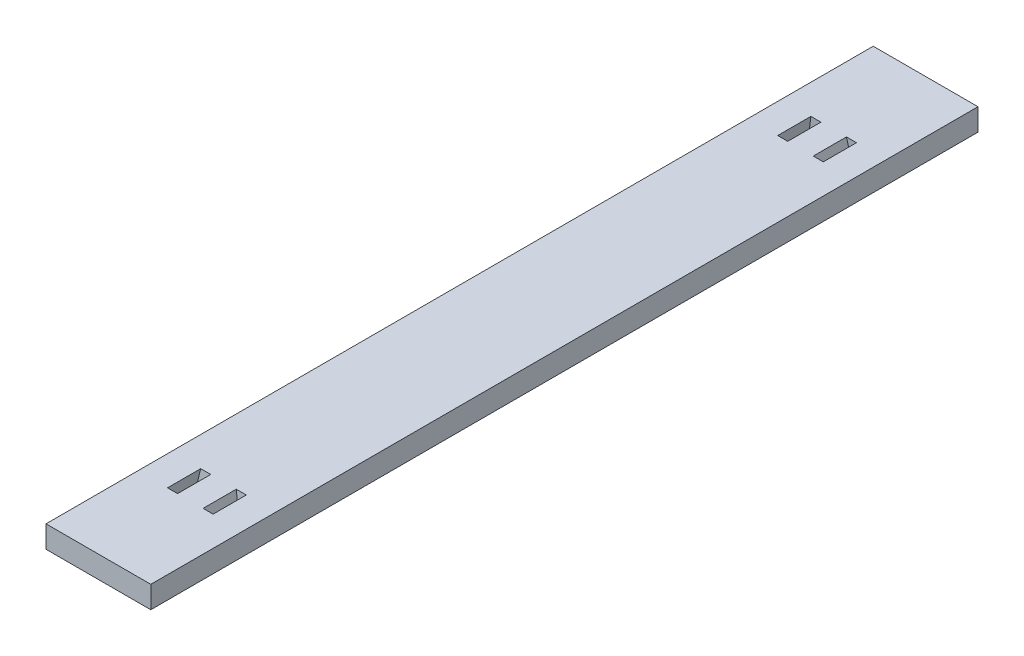
SolidWorks part; units mm, degrees
ref_plane "前基準面" through (0, 0, 0) normal (0, 0, 1) x (1, 0, 0)
ref_plane "上基準面" through (0, 0, 0) normal (0, 1, 0) x (1, 0, 0)
ref_plane "右基準面" through (0, 0, 0) normal (1, 0, 0) x (0, 0, -1)
sketch "草圖1" plane through (0, 0, 0) normal (0, 0, 1) x (1, 0, 0)
  line L1 (0, 0) -> (190, 0)
  line L2 (0, 0) -> (0, -40)
  line L3 (0, -40) -> (190, -40)
  line L4 (190, 0) -> (190, -40)
  dimension "D1" = 190
  dimension "D2" = 40
extrude "填料-伸長1" add sketch "草圖1" against normal blind 1500
sketch "草圖2" plane through (0, 0, 0) normal (0, 0, 1) x (1, 0, 0)
  line L0 (119.7, 0) -> (210.6, -606) construction
  line L1 (159.7, 0) -> (250.6, -606) construction
  line L2 (-79.8675, -606) -> (316.1742, -606) construction
  line L3 (190, -40) -> (190, 0) construction
  line L4 (0, 0) -> (190, 0) construction
  line L5 (0, 0) -> (190, -40) construction
  line L6 (190, -40) -> (0, -40) construction
  line L7 (0, -40) -> (190, 0) construction
  line L9 (95, 28.6037) -> (95, -85.0059) construction
  point P12 (125.7, -40)
  point P18 (165.7, -40)
  dimension "D1" = 606
  dimension "D2" = 30.3
  dimension "D3" = 40
  dimension "D4" = 60.6
sketch "草圖3" plane through (0, 0, 0) normal (1, 0, 0) x (0, 0, -1)
  line L0 (166.7, 0) -> (121.2, -606) construction
  line L1 (1500, 0) -> (0, 0) construction
  line L2 (0, -606) -> (1500, -606) construction
  line L3 (0, 0) -> (0, -606) construction
  line L4 (226.8689, 0) -> (181.5608, -603.4444) construction
  line L5 (750, 0) -> (750, -606) construction
  line L6 (0, 0) -> (1500, 0) construction
  line L7 (1500, -40) -> (0, -40) construction
  line L8 (1273.1311, 0) -> (1318.4392, -603.4444) construction
  line L9 (1333.3, 0) -> (1378.8, -606) construction
  point P8 (0, -606)
  point P20 (750, 0)
  point P28 (163.6967, -40)
  point P29 (223.8656, -40)
  dimension "D1" = 166.7
  dimension "D2" = 121.2
  dimension "D3" = 60
sketch "草圖4" plane through (0, 0, 0) normal (0, 1, 0) x (1, 0, 0)
  line L0 (0, 226.8689) -> (190, 226.8689) construction
  line L1 (0, 1500) -> (0, 0) construction
  line L2 (190, 1500) -> (190, 0) construction
  line L3 (0, 0) -> (0, 1500) construction
  line L4 (0, 166.7) -> (190, 166.7) construction
  line L5 (0, 0) -> (0, 1500) construction
  line L6 (0, 1500) -> (0, 0) construction
  line L8 (118.1533, 226.8689) -> (136.3333, 226.8689)
  line L9 (118.1533, 226.8689) -> (118.1533, 166.7)
  line L10 (118.1533, 166.7) -> (136.3333, 166.7)
  line L11 (0, 0) -> (190, 0) construction
  line L12 (136.3333, 226.8689) -> (136.3333, 166.7)
  line L16 (118.1533, 0) -> (118.1533, 1500) construction
  line L17 (-79.8675, 0) -> (316.1742, 0) construction
  line L18 (190, 1500) -> (0, 1500) construction
  line L19 (159.7, 0) -> (159.7, 1500) construction
  point P10 (0, 226.8689)
  point P11 (0, 166.7)
  point P14 (119.7, 0)
  point P17 (159.7, 0)
  dimension "D1" = 18.18
ref_plane "平面1" through (0, -40, 0) normal (0, 1, 0) x (-1, 0, 0)
sketch "草圖5" plane through (0, -40, 0) normal (0, 1, 0) x (-1, 0, 0)
  line L0 (-165.7, 0) -> (-165.7, -1500) construction
  line L1 (-190, -1500) -> (0, -1500) construction
  line L2 (-125.7, 0) -> (-125.7, -1500) construction
  line L3 (0, -163.6967) -> (-190, -163.6967) construction
  line L4 (-190, -1500) -> (-190, 0) construction
  line L5 (0, -223.8656) -> (-190, -223.8656) construction
  line L6 (-118.1533, -166.7) -> (-136.3333, -166.7) construction
  line L7 (-125.7, -163.6967) -> (-143.88, -163.6967)
  line L8 (-125.7, -163.6967) -> (-125.7, -223.8656)
  line L9 (-125.7, -223.8656) -> (-143.88, -223.8656)
  line L10 (-143.88, -163.6967) -> (-143.88, -223.8656)
  line L11 (-190, 0) -> (0, 0) construction
  line L12 (-95, 0) -> (-95, -1500) construction
  line L13 (0, -750) -> (-190, -750) construction
  line L14 (0, -1500) -> (0, 0) construction
  point P22 (-95, 0)
  point P23 (-95, -1500)
ref_axis "基準軸1" through (143.88, -40, -163.6967) along (-0.1849, 0.98, -0.0736)
extrude "除料-伸長1" cut sketch "草圖4" along direction (-0.1849, 0.98, -0.0736) on the side against the normal blind 1500
ref_plane "平面2" through (95, 0, 0) normal (1, 0, 0) x (0, 0, -1)
ref_plane "平面3" through (0, 0, -750) normal (0, 0, 1) x (1, 0, 0)
mirror "鏡射1" about plane through (0, 0, -750) normal (0, 0, 1) of "除料-伸長1"
mirror "鏡射2" about plane through (95, 0, 0) normal (1, 0, 0) of "鏡射1"
